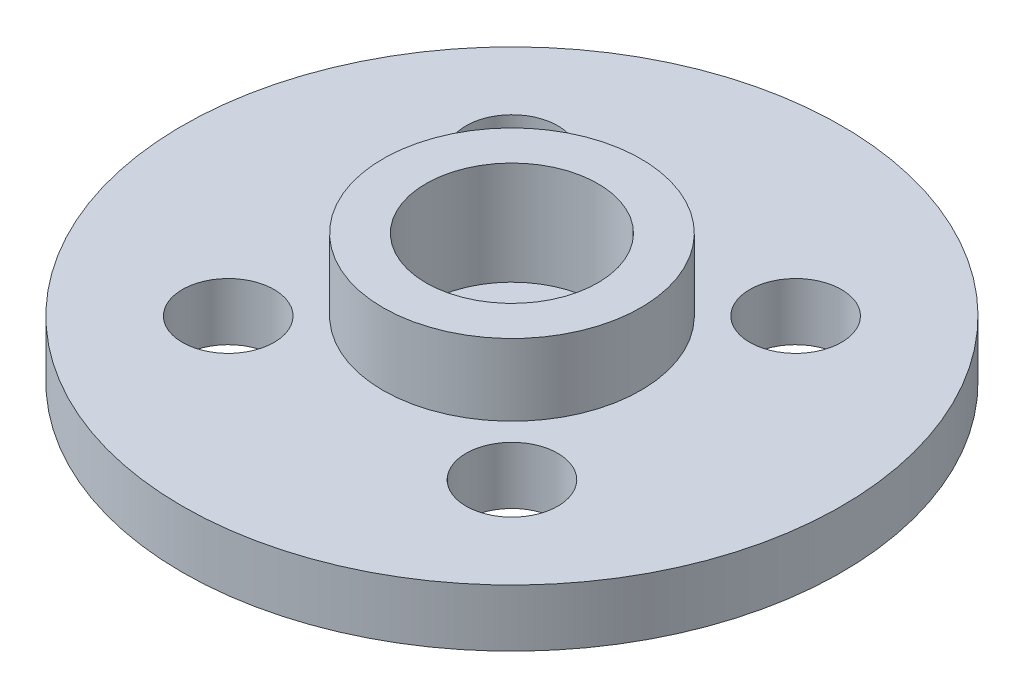
SolidWorks part; units mm, degrees
ref_plane "Front Plane" through (0, 0, 0) normal (0, 0, 1) x (1, 0, 0)
ref_plane "Top Plane" through (0, 0, 0) normal (0, 1, 0) x (1, 0, 0)
ref_plane "Right Plane" through (0, 0, 0) normal (1, 0, 0) x (0, 0, -1)
sketch "Sketch1" plane through (0, 0, 0) normal (0, 1, 0) x (1, 0, 0)
  line L0 (-4.9497, 4.9497) -> (4.9497, 4.9497) construction
  line L1 (4.9497, 4.9497) -> (4.9497, -4.9497) construction
  circle A0 centre (0, 0) radius 11.5
  circle A1 centre (-4.9497, 4.9497) radius 1.6
  circle A2 centre (4.9497, 4.9497) radius 1.6
  circle A3 centre (4.9497, -4.9497) radius 1.6
  circle A4 centre (-4.9497, -4.9497) radius 1.6
  circle A5 centre (0, 0) radius 7 construction
  circle A6 centre (0, 0) radius 1.6
  dimension "D1" = 23
  dimension "D2" = 3.2
  dimension "D3" = 3.2
  dimension "D4" = 14
extrude "Boss-Extrude1" add sketch "Sketch1" along normal blind 2
sketch "Sketch2" plane through (0, 2, 0) normal (0, 1, 0) x (1, 0, 0)
  circle A0 centre (0, 0) radius 4.5
  circle A1 centre (0, 0) radius 1.6 construction
  circle A2 centre (0, 0) radius 1.6
  dimension "D1" = 9
extrude "Boss-Extrude2" add sketch "Sketch2" along normal blind 2.5
sketch "Sketch3" plane through (0, 4.5, 0) normal (0, 1, 0) x (1, 0, 0)
  circle A0 centre (0, 0) radius 3
  dimension "D1" = 6
extrude "Cut-Extrude1" cut sketch "Sketch3" against normal blind 3.6
sketch "Sketch7" plane through (0, 4.5, 0) normal (0, 1, 0) x (1, 0, 0)
  line L0 (-1.035, 2.4395) -> (-0.843, 2.5123)
  line L1 (-0.843, 2.5123) -> (-0.7982, 2.6036)
  line L2 (-0.7982, 2.6036) -> (-0.694, 2.8157)
  line L3 (-0.694, 2.8157) -> (-0.5032, 2.6763)
  line L4 (-0.5032, 2.6763) -> (-0.4211, 2.6163)
  line L5 (-0.4211, 2.6163) -> (-0.2173, 2.6411)
  line L6 (-0.2173, 2.6411) -> (-0.1519, 2.719)
  line L7 (-0.1519, 2.719) -> (0, 2.9)
  line L8 (0, 2.9) -> (0.1519, 2.719)
  line L9 (0.1519, 2.719) -> (0.2173, 2.6411)
  line L10 (0.2173, 2.6411) -> (0.4211, 2.6163)
  line L11 (0.4211, 2.6163) -> (0.5032, 2.6763)
  line L12 (0.5032, 2.6763) -> (0.694, 2.8157)
  line L13 (0.694, 2.8157) -> (0.7982, 2.6036)
  line L14 (0.7982, 2.6036) -> (0.843, 2.5123)
  line L15 (0.843, 2.5123) -> (1.035, 2.4395)
  line L16 (1.035, 2.4395) -> (1.1291, 2.4781)
  line L17 (1.1291, 2.4781) -> (1.3477, 2.5678)
  line L18 (1.3477, 2.5678) -> (1.3981, 2.337)
  line L19 (1.3981, 2.337) -> (1.4197, 2.2376)
  line L20 (1.4197, 2.2376) -> (1.5887, 2.1209)
  line L21 (1.5887, 2.1209) -> (1.6893, 2.1359)
  line L22 (1.6893, 2.1359) -> (1.9231, 2.1707)
  line L23 (1.9231, 2.1707) -> (1.9167, 1.9345)
  line L24 (1.9167, 1.9345) -> (1.914, 1.8328)
  line L25 (1.914, 1.8328) -> (2.0501, 1.6791)
  line L26 (2.0501, 1.6791) -> (2.1514, 1.6696)
  line L27 (2.1514, 1.6696) -> (2.3867, 1.6474)
  line L28 (2.3867, 1.6474) -> (2.324, 1.4196)
  line L29 (2.324, 1.4196) -> (2.297, 1.3215)
  line L30 (2.297, 1.3215) -> (2.3924, 1.1397)
  line L31 (2.3924, 1.1397) -> (2.4884, 1.1062)
  line L32 (2.4884, 1.1062) -> (2.7115, 1.0284)
  line L33 (2.7115, 1.0284) -> (2.5962, 0.8221)
  line L34 (2.5962, 0.8221) -> (2.5465, 0.7334)
  line L35 (2.5465, 0.7334) -> (2.5956, 0.534)
  line L36 (2.6809, 0.4785) -> (2.5956, 0.534) construction
  line L37 (2.5956, 0.534) -> (2.6809, 0.4785)
  line L38 (2.6809, 0.4785) -> (2.8789, 0.3496)
  line L39 (2.6809, 0.4785) -> (2.8789, 0.3496)
  line L40 (2.7175, 0.177) -> (2.648, 0.1027)
  line L41 (2.648, 0.1027) -> (2.648, -0.1027)
  line L42 (2.648, -0.1027) -> (2.7175, -0.177)
  line L43 (2.7175, -0.177) -> (2.8789, -0.3496)
  line L44 (2.8789, -0.3496) -> (2.6809, -0.4785)
  line L45 (2.6809, -0.4785) -> (2.5956, -0.534)
  line L46 (2.5956, -0.534) -> (2.5465, -0.7334)
  line L47 (2.5465, -0.7334) -> (2.5962, -0.8221)
  line L48 (2.5962, -0.8221) -> (2.7115, -1.0284)
  line L49 (2.7115, -1.0284) -> (2.4884, -1.1062)
  line L50 (2.4884, -1.1062) -> (2.3924, -1.1397)
  line L51 (2.3924, -1.1397) -> (2.4884, -1.1062) construction
  line L52 (2.3924, -1.1397) -> (2.297, -1.3215)
  line L53 (2.297, -1.3215) -> (2.324, -1.4196)
  line L54 (2.324, -1.4196) -> (2.3867, -1.6474)
  line L55 (2.3867, -1.6474) -> (2.1514, -1.6696)
  line L56 (2.1514, -1.6696) -> (2.0501, -1.6791)
  line L57 (2.0501, -1.6791) -> (1.914, -1.8328)
  line L58 (1.914, -1.8328) -> (1.9167, -1.9345)
  line L59 (1.9167, -1.9345) -> (1.9231, -2.1707)
  line L60 (1.9231, -2.1707) -> (1.6893, -2.1359)
  line L61 (1.6893, -2.1359) -> (1.5887, -2.1209)
  line L62 (1.5887, -2.1209) -> (1.4197, -2.2376)
  line L63 (1.4197, -2.2376) -> (1.3981, -2.337)
  line L64 (1.3981, -2.337) -> (1.3477, -2.5678)
  line L65 (1.3477, -2.5678) -> (1.1291, -2.4781)
  line L66 (1.1291, -2.4781) -> (1.035, -2.4395)
  line L67 (1.035, -2.4395) -> (0.843, -2.5123)
  line L68 (0.843, -2.5123) -> (0.7982, -2.6036)
  line L69 (0.7982, -2.6036) -> (0.694, -2.8157)
  line L70 (0.694, -2.8157) -> (0.5032, -2.6763)
  line L71 (0.5032, -2.6763) -> (0.4211, -2.6163)
  line L72 (0.4211, -2.6163) -> (0.2173, -2.6411)
  line L73 (0.2173, -2.6411) -> (0.1519, -2.719)
  line L74 (0.1519, -2.719) -> (0, -2.9)
  line L75 (0, -2.9) -> (-0.1519, -2.719)
  line L76 (-0.1519, -2.719) -> (-0.2173, -2.6411)
  line L77 (-0.2173, -2.6411) -> (-0.4211, -2.6163)
  line L78 (-0.4211, -2.6163) -> (-0.5032, -2.6763)
  line L79 (-0.5032, -2.6763) -> (-0.694, -2.8157)
  line L80 (-0.694, -2.8157) -> (-0.7982, -2.6036)
  line L81 (-0.7982, -2.6036) -> (-0.843, -2.5123)
  line L82 (-0.843, -2.5123) -> (-1.035, -2.4395)
  line L83 (-1.035, -2.4395) -> (-1.1291, -2.4781)
  line L84 (-1.1291, -2.4781) -> (-1.3477, -2.5678)
  line L85 (-1.3477, -2.5678) -> (-1.3981, -2.337)
  line L86 (-1.3981, -2.337) -> (-1.4197, -2.2376)
  line L87 (-1.4197, -2.2376) -> (-1.5887, -2.1209)
  line L88 (-1.5887, -2.1209) -> (-1.6893, -2.1359)
  line L89 (-1.6893, -2.1359) -> (-1.9231, -2.1707)
  line L90 (-1.9231, -2.1707) -> (-1.9167, -1.9345)
  line L91 (-1.9167, -1.9345) -> (-1.914, -1.8328)
  line L92 (-1.914, -1.8328) -> (-2.0501, -1.6791)
  line L93 (-2.0501, -1.6791) -> (-2.1514, -1.6696)
  line L94 (-2.1514, -1.6696) -> (-2.3867, -1.6474)
  line L95 (-2.3867, -1.6474) -> (-2.324, -1.4196)
  line L96 (-2.324, -1.4196) -> (-2.297, -1.3215)
  line L97 (-2.297, -1.3215) -> (-2.3924, -1.1397)
  line L98 (-2.3924, -1.1397) -> (-2.4884, -1.1062)
  line L99 (-2.4884, -1.1062) -> (-2.7115, -1.0284)
  line L100 (-2.7115, -1.0284) -> (-2.5962, -0.8221)
  line L101 (-2.5962, -0.8221) -> (-2.5465, -0.7334)
  line L102 (-2.5465, -0.7334) -> (-2.5956, -0.534)
  line L103 (-2.5956, -0.534) -> (-2.6809, -0.4785)
  line L104 (-2.6809, -0.4785) -> (-2.8789, -0.3496)
  line L105 (-2.8789, -0.3496) -> (-2.7175, -0.177)
  line L106 (-2.7175, -0.177) -> (-2.648, -0.1027)
  line L107 (-2.648, -0.1027) -> (-2.648, 0.1027)
  line L108 (-2.648, 0.1027) -> (-2.7175, 0.177)
  line L109 (-2.7175, 0.177) -> (-2.8789, 0.3496)
  line L110 (-2.8789, 0.3496) -> (-2.6809, 0.4785)
  line L111 (-2.6809, 0.4785) -> (-2.5956, 0.534)
  line L112 (-2.5956, 0.534) -> (-2.5465, 0.7334)
  line L113 (-2.5465, 0.7334) -> (-2.5962, 0.8221)
  line L114 (-2.5962, 0.8221) -> (-2.7115, 1.0284)
  line L115 (-2.7115, 1.0284) -> (-2.4884, 1.1062)
  line L116 (-2.4884, 1.1062) -> (-2.3924, 1.1397)
  line L117 (-2.3924, 1.1397) -> (-2.297, 1.3215)
  line L118 (-2.297, 1.3215) -> (-2.324, 1.4196)
  line L119 (-2.324, 1.4196) -> (-2.3867, 1.6474)
  line L120 (-2.3867, 1.6474) -> (-2.1514, 1.6696)
  line L121 (-2.1514, 1.6696) -> (-2.0501, 1.6791)
  line L122 (-2.0501, 1.6791) -> (-1.914, 1.8328)
  line L123 (-1.914, 1.8328) -> (-1.9167, 1.9345)
  line L124 (-1.9167, 1.9345) -> (-1.9231, 2.1707)
  line L125 (-1.9231, 2.1707) -> (-1.6893, 2.1359)
  line L126 (-1.6893, 2.1359) -> (-1.5887, 2.1209)
  line L127 (-1.5887, 2.1209) -> (-1.4197, 2.2376)
  line L128 (-1.4197, 2.2376) -> (-1.3981, 2.337)
  line L129 (-1.3981, 2.337) -> (-1.3477, 2.5678)
  line L130 (-1.3477, 2.5678) -> (-1.1291, 2.4781)
  line L131 (-1.1291, 2.4781) -> (-1.035, 2.4395)
  line L132 (-0.843, 2.5123) -> (-0.7982, 2.6036)
  line L133 (-0.694, 2.8157) -> (-0.5032, 2.6763)
  line L134 (-0.4211, 2.6163) -> (-0.2173, 2.6411)
  line L135 (-0.1519, 2.719) -> (0, 2.9)
  line L136 (0.1519, 2.719) -> (0.2173, 2.6411)
  line L137 (0.4211, 2.6163) -> (0.5032, 2.6763)
  line L138 (0.694, 2.8157) -> (0.7982, 2.6036)
  line L139 (1.035, 2.4395) -> (1.3477, 2.5678)
  line L140 (1.3981, 2.337) -> (1.4197, 2.2376)
  line L141 (1.5887, 2.1209) -> (1.6893, 2.1359)
  line L142 (1.9231, 2.1707) -> (1.9167, 1.9345)
  line L143 (1.914, 1.8328) -> (2.0501, 1.6791)
  line L144 (2.1514, 1.6696) -> (2.3867, 1.6474)
  line L145 (2.324, 1.4196) -> (2.297, 1.3215)
  line L146 (2.3924, 1.1397) -> (2.7115, 1.0284)
  line L147 (2.5962, 0.8221) -> (2.5465, 0.7334)
  line L148 (2.8789, 0.3496) -> (2.7175, 0.177)
extrude "Cut-Extrude2" [suppressed] cut sketch "Sketch7" against normal up to surface (3.6 mm away) contours L148 L38 L37 L35 L34 L33 L32 L31 L30 L29 L28 L27 L26 L25 L24 L23 L22 L21 L20 L19 L18 L17 L16 L15 L14 L13 L12 L11 L10 L9 L8 L7 L6 L5 L4 L3 L2 L1 L0 L131 L130 L129 L128 L127 L126 L125 L124 L123 L122 L121 L120
chamfer "Chamfer1" [suppressed] distance 0.1 angle 45
